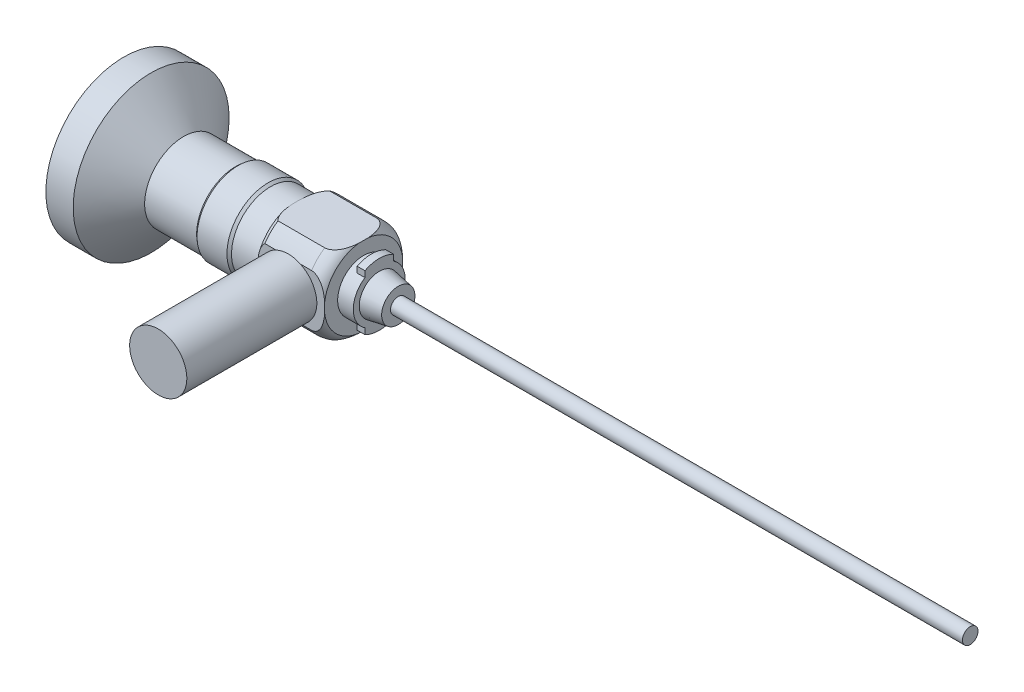
SolidWorks part; units mm, degrees
material "AISI 316 Stainless Steel Sheet (SS)"
ref_plane "Front Plane" through (0, 0, 0) normal (0, 0, 1) x (1, 0, 0)
ref_plane "Top Plane" through (0, 0, 0) normal (0, 1, 0) x (1, 0, 0)
ref_plane "Right Plane" through (0, 0, 0) normal (1, 0, 0) x (0, 0, -1)
ref_axis "Axis1" through (88.99, 0, 0) along (-1, 0, 0)
sketch "Sketch1" plane through (0, 0, 0) normal (0, 0, 1) x (1, 0, 0)
  line L0 (-74.5697, 0) -> (-77.8697, -15) construction
  line L1 (-77.8697, -15) -> (-72.6197, -15)
  line L2 (-72.6197, -15) -> (-66.3697, -7.5)
  line L3 (-66.3697, -7.5) -> (-56.3697, -7.5)
  line L4 (-56.3697, -7.5) -> (-55.8897, -7.9)
  line L5 (-55.8897, -7.9) -> (-50.1397, -7.9)
  line L6 (-50.1397, -7.9) -> (-49.6597, -7.5)
  line L7 (-49.6597, -7.5) -> (-44.6597, -7.5)
  line L8 (88.99, 0) -> (-88.99, 0) construction
  line L9 (-74.5697, 0) -> (-25.0835, 0)
  line L10 (-43.2452, -9) -> (-34.2597, -9)
  line L11 (-31.7461, -7.5592) -> (-31.7461, -5)
  line L12 (-31.7461, -5) -> (-30.2461, -5)
  line L13 (-30.2461, -5) -> (-30.2461, -6)
  line L14 (-30.2461, -6) -> (-28.7461, -6)
  line L15 (-28.7461, -6) -> (-28.7461, -3.85)
  line L16 (-28.7461, -3.85) -> (-25.0835, -3.2)
  line L17 (-25.0835, -3.2) -> (-25.0835, 0)
  arc A0 (-74.5697, 0) -> (-77.8697, -15) centre (-129.3209, 4.1823) cw
  arc A1 (-44.6597, -7.5) -> (-40.5597, -9) centre (-41.9025, -6.3168) ccw
  arc A2 (-34.2597, -9) -> (-31.7461, -7.5592) centre (-34.3096, -6) ccw
  point P12 (-40.5597, -9)
  point P16 (-34.2597, -9)
  point P17 (-44.6597, -9)
  point P18 (-37.4097, -9)
  point P20 (-30.1597, -9)
  dimension "D4" = 11.5
  dimension "D12" = 9
  dimension "D13" = 3.15
  dimension "D15" = 5
  dimension "D1" = 5.25
  dimension "D2" = 15
  dimension "D3" = 3.3
  dimension "D5" = 7.5
  dimension "D6" = 5.75
  dimension "D7" = 7.9
  dimension "D8" = 7.5
  dimension "D9" = 10
  dimension "D10" = 5
  dimension "D11" = 14.5
  dimension "D14" = 3.15
  dimension "D16" = 6
  dimension "D17" = 1.5
  dimension "D18" = 1.5
  dimension "D19" = 3.85
  dimension "D20" = 3.2
revolve "Revolve1" add sketch "Sketch1" angle 360 about axis through (88.99, 0, 0) along (-1, 0, 0) region at (-53.5304, -4.7691, 0)
sketch "Sketch2" plane through (-31.7461, 0, 0) normal (1, 0, 0) x (0, 0, -1)
  line L0 (0, 9) -> (0, -9)
  line L1 (12.4327, -7.5) -> (-12.4327, -7.5)
  line L2 (12.4327, -7.5) -> (12.4327, 7.5) construction
  line L3 (12.4327, 7.5) -> (-12.4327, 7.5)
  line L4 (-12.4327, -7.5) -> (-12.4327, 7.5) construction
  line L5 (12.4327, 7.5) -> (-12.4327, -7.5) construction
  line L6 (12.4327, 7.5) -> (12.4327, 11.5013)
  line L7 (12.4327, 11.5013) -> (-12.4327, 11.5013)
  line L8 (-12.4327, 11.5013) -> (-12.4327, 7.5)
  line L9 (-12.4327, -7.5) -> (-12.4327, -12.9232)
  line L10 (-12.4327, -12.9232) -> (12.4327, -12.9232)
  line L11 (12.4327, -12.9232) -> (12.4327, -7.5)
  circle A0 centre (0, 0) radius 9 construction
  circle A1 centre (0, 0) radius 9
  dimension "D1" = 15
extrude "Cut-Extrude1" cut sketch "Sketch2" against normal blind 15 contours L9 L10 L11 L1 | L8 L3 L6 L7
pattern_circular "CirPattern1" count 2 every 90 about axis through (88.99, 0, 0) along (-1, 0, 0) of "Cut-Extrude1"
sketch "Sketch3" plane through (-28.7461, 0, 0) normal (1, 0, 0) x (0, 0, -1)
  line L0 (2.75, 6.4372) -> (2.75, -6.4372) construction
  line L1 (-2.75, -6.4372) -> (-2.75, 6.4372) construction
  line L2 (2.75, -6.4372) -> (-2.75, 6.4372) construction
  line L3 (2.75, -4.1758) -> (2.75, -6.4372)
  line L4 (2.75, -6.4372) -> (-2.75, -6.4372) construction
  line L5 (-2.75, -6.4372) -> (-2.75, -4.1758)
  line L6 (2.75, 4.1758) -> (2.75, 6.4372)
  line L7 (2.75, 6.4372) -> (-2.75, 6.4372) construction
  line L8 (-2.75, 6.4372) -> (-2.75, 4.1758)
  line L9 (2.75, 6.4372) -> (6.4302, 6.4372)
  line L10 (6.4302, 6.4372) -> (5.9638, -6.4372)
  line L11 (5.9638, -6.4372) -> (2.75, -6.4372)
  line L12 (-2.75, -6.4372) -> (-6.2806, -6.4372)
  line L13 (-6.2806, -6.4372) -> (-6.2806, 6.4372)
  line L14 (-6.2806, 6.4372) -> (-2.75, 6.4372)
  circle A0 centre (0, 0) radius 6 construction
  circle A1 centre (0, 0) radius 6 construction
  arc A2 (2.75, -4.1758) -> (2.75, 4.1758) centre (0, 0) ccw
  arc A3 (-2.75, 4.1758) -> (-2.75, -4.1758) centre (0, 0) ccw
  point P3 (7, 0)
  point P4 (0, 0)
  dimension "D1" = 10
  dimension "D3" = 5.5
extrude "Cut-Extrude2" cut sketch "Sketch3" against normal up to surface (1.5 mm away) up to face at (-30.2461, 0, -6)
sketch "Sketch4" plane through (0, 0, 7.5) normal (0, 0, 1) x (1, 0, 0)
  line L0 (-34.2597, 4.9749) -> (-43.2452, -4.9749) construction
  circle A0 centre (-38.7525, 0) radius 5.5
  dimension "D1" = 11
extrude "Boss-Extrude1" add sketch "Sketch4" along normal blind 25
sketch "Sketch5" plane through (-25.0835, 0, 0) normal (1, 0, 0) x (0, 0, -1)
  circle A0 centre (0, 0) radius 1.5
  dimension "D1" = 3
extrude "Boss-Extrude2" add sketch "Sketch5" along normal blind 110
sketch "Sketch6" plane through (0, 0, 0) normal (0, 0, 1) x (1, 0, 0)
  line L0 (84.9165, 0) -> (85.1501, 0)
  line L1 (84.9165, 0) -> (92.6353, 0)
  line L2 (84.9165, -1.5) -> (84.9165, 1.5) construction
  line L3 (84.9165, -1.5) -> (84.9165, 1.5)
  line L4 (84.9165, 0) -> (92.6353, -7.7188)
  line L5 (92.6353, -7.7188) -> (92.6353, 0)
  dimension "D2" = 45
revolve "Revolve2" [suppressed] add sketch "Sketch6" angle 360 about L1
